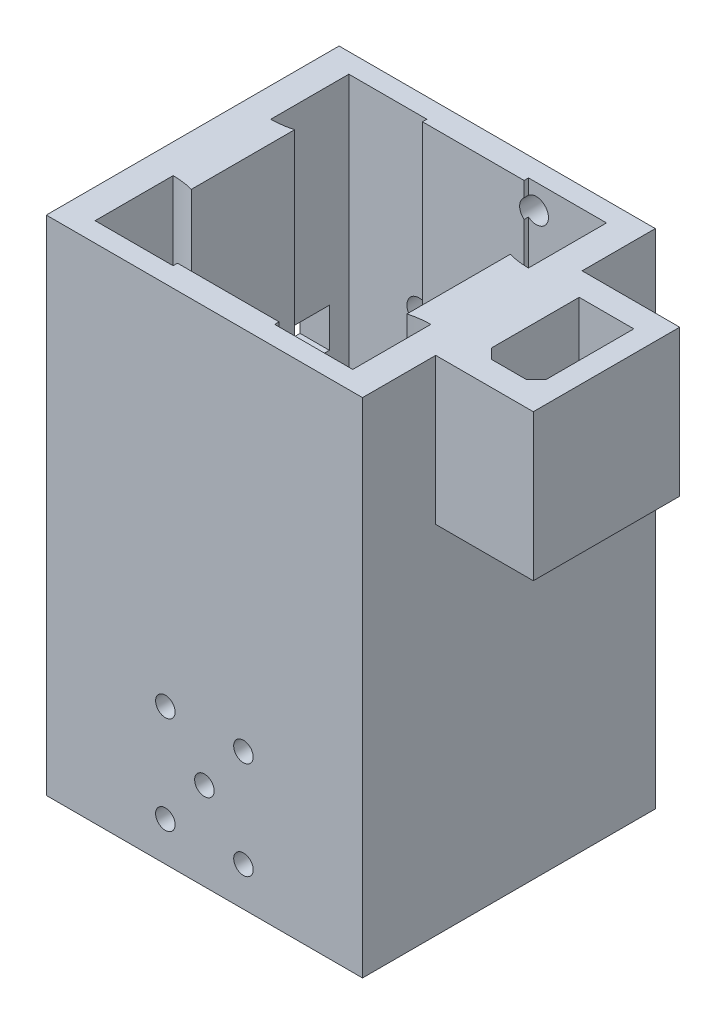
SolidWorks part; units mm, degrees
ref_plane "Front Plane" through (0, 0, 0) normal (0, 0, 1) x (1, 0, 0)
ref_plane "Top Plane" through (0, 0, 0) normal (0, 1, 0) x (1, 0, 0)
ref_plane "Right Plane" through (0, 0, 0) normal (1, 0, 0) x (0, 0, -1)
sketch "Sketch1" plane through (0, 0, 0) normal (0, 1, 0) x (1, 0, 0)
  line L0 (16.2, 0) -> (16.2, -30) construction
  line L1 (0, 0) -> (32.4, 0)
  line L2 (0, 0) -> (0, -30)
  line L3 (0, -30) -> (32.4, -30)
  line L4 (32.4, 0) -> (32.4, -30)
  line L5 (0, -15) -> (32.4, -15) construction
  circle A0 centre (6.2, -5) radius 1.75
  circle A1 centre (26.2, -5) radius 1.75
  circle A2 centre (26.2, -25) radius 1.75
  circle A3 centre (6.2, -25) radius 1.75
  dimension "D3" = 3.5
  dimension "D8" = 20
  dimension "D1" = 30
  dimension "D2" = 32.4
  dimension "D6" = 10
  dimension "D7" = 10
  dimension "D9" = 20
  dimension "D4" = 2
  dimension "D5" = 2
extrude "Boss-Extrude1" add sketch "Sketch1" along normal blind 25
sketch "Sketch2" plane through (0, 25, 0) normal (0, 1, 0) x (1, 0, 0)
  line L1 (16.2, 0) -> (16.2, -30) construction
  line L2 (32.4, 0) -> (0, 0) construction
  line L3 (0, -30) -> (32.4, -30) construction
  line L4 (0, -15) -> (32.4, -15) construction
  line L5 (0, 0) -> (0, -30) construction
  line L6 (32.4, -30) -> (32.4, 0) construction
  circle A0 centre (16.2, -15) radius 4
  dimension "D1" = 8
extrude "Cut-Extrude1" cut sketch "Sketch2" against normal blind 20
sketch "Sketch3" plane through (0, 25, 0) normal (0, 1, 0) x (1, 0, 0)
  line L0 (3, -10) -> (3, -20)
  line L1 (0, 0) -> (32.4, 0)
  line L2 (0, 0) -> (0, -30)
  line L3 (0, -30) -> (32.4, -30)
  line L4 (32.4, 0) -> (32.4, -30)
  line L5 (3, -2) -> (29.4, -2)
  line L6 (3, -2) -> (3, -28)
  line L7 (3, -28) -> (29.4, -28)
  line L8 (29.4, -2) -> (29.4, -28)
  line L9 (11, -28) -> (21.4, -28)
  line L10 (29.4, -20) -> (29.4, -10)
  line L11 (21.4, -2) -> (11, -2)
  arc A0 (11, -2) -> (3, -10) centre (3, -2) cw
  arc A1 (21.4, -28) -> (29.4, -20) centre (29.4, -28) cw
  arc A2 (29.4, -10) -> (21.4, -2) centre (29.4, -2) cw
  arc A3 (3, -20) -> (11, -28) centre (3, -28) cw
  circle M17 centre (16.2, -15) radius 4
  line M20 (0, 0) -> (0, -30)
  line M21 (0, -30) -> (32.4, -30)
  line M22 (32.4, -30) -> (32.4, 0)
  line M23 (32.4, 0) -> (0, 0)
  dimension "D5" = 8
  dimension "D6" = 8
  dimension "D7" = 8
  dimension "D8" = 8
  dimension "D1" = 3
  dimension "D2" = 3
  dimension "D3" = 2
  dimension "D4" = 2
extrude "Boss-Extrude2" add sketch "Sketch3" along normal blind 3 contours L5 L8 L7 L6 L0 M23 M20 M21 M22 | L0 A3 L7 A1 L8 A2 L5 A0 M17 region at (8.9189, 25, 7.9189) region at (16.2, 25, 0.4416)
sketch "Sketch4" plane through (0, 28, 0) normal (0, 1, 0) x (1, 0, 0)
  line L0 (16.2, 0) -> (16.2, -30) construction
  line L9 (32.4, 0) -> (0, 0) construction
  line L10 (0, -30) -> (32.4, -30) construction
  line L11 (32.4, -15) -> (0, -15) construction
  line L12 (5.15, -20.2943) -> (5.15, -9.7057)
  line L13 (0, 0) -> (0, -30) construction
  line L14 (32.4, -30) -> (32.4, 0) construction
  line L15 (29.4, -20) -> (29.4, -28) construction
  line L16 (21.4, -28) -> (29.4, -28) construction
  line L17 (3, -28) -> (11, -28) construction
  line L18 (3, -20) -> (3, -28) construction
  line L19 (3, -2) -> (11, -2) construction
  line L20 (21.4, -2) -> (29.4, -2) construction
  line L21 (29.4, -2) -> (29.4, -10) construction
  line L22 (3, -2) -> (3, -10) construction
  line L23 (0, -30) -> (32.4, -30)
  line L24 (0, 0) -> (0, -30)
  line L25 (32.4, 0) -> (0, 0)
  line L26 (32.4, -30) -> (32.4, 0)
  line L27 (29.4, -20) -> (29.4, -28)
  line L28 (21.4, -28) -> (29.4, -28)
  line L29 (3, -28) -> (11, -28)
  line L30 (3, -20) -> (3, -28)
  line L31 (3, -2) -> (11, -2)
  line L32 (21.4, -2) -> (29.4, -2)
  line L33 (29.4, -2) -> (29.4, -10)
  line L34 (3, -2) -> (3, -10)
  line L35 (10.9873, -2.45) -> (21.4127, -2.45)
  line L36 (27.25, -9.7057) -> (27.25, -20.2943)
  line L37 (10.9873, -27.55) -> (21.4127, -27.55)
  arc A0 (29.4, -20) -> (21.4, -28) centre (29.4, -28) ccw construction
  arc A1 (11, -28) -> (3, -20) centre (3, -28) ccw construction
  arc A2 (21.4, -2) -> (29.4, -10) centre (29.4, -2) ccw construction
  arc A3 (3, -10) -> (11, -2) centre (3, -2) ccw construction
  arc A4 (29.4, -20) -> (27.25, -20.2943) centre (29.4, -28) ccw
  arc A5 (11, -28) -> (10.9873, -27.55) centre (3, -28) ccw
  arc A6 (21.4, -2) -> (21.4127, -2.45) centre (29.4, -2) ccw
  arc A7 (3, -10) -> (5.15, -9.7057) centre (3, -2) ccw
  arc A8 (10.9873, -2.45) -> (11, -2) centre (3, -2) ccw
  arc A9 (5.15, -20.2943) -> (3, -20) centre (3, -28) ccw
  arc A10 (21.4127, -27.55) -> (21.4, -28) centre (29.4, -28) ccw
  arc A11 (27.25, -9.7057) -> (29.4, -10) centre (29.4, -2) ccw
  point P15 (16.2, -15)
  dimension "D1" = 22.1
  dimension "D2" = 11.05
  dimension "D3" = 25.1
  dimension "D4" = 12.55
extrude "Boss-Extrude3" add sketch "Sketch4" along normal blind 23.5
sketch "Sketch5" plane through (0, 0, 0) normal (0, 0, -1) x (-1, 0, 0)
  line L0 (-32.4, 28) -> (0, 28) construction
  line L1 (-32.4, 28) -> (0, 28)
  line L2 (-5.15, 28) -> (-5.15, 36.9803) construction
  line L3 (0, 51.5) -> (0, 0) construction
  line L4 (-27.25, 28) -> (-27.25, 39.4314) construction
  line L5 (-32.4, 51.5) -> (-32.4, 0) construction
  line L6 (-16.2, 28) -> (-16.2, 36.5707) construction
  circle A0 centre (-22.2, 49) radius 1.25
  circle A1 centre (-10.2, 34) radius 1.25
  dimension "D6" = 2.5
  dimension "D7" = 2.5
  dimension "D1" = 6
  dimension "D2" = 12
  dimension "D3" = 5.15
  dimension "D4" = 5.15
  dimension "D5" = 6
  dimension "D8" = 15
extrude "Cut-Extrude2" cut sketch "Sketch5" along direction (0, 0, 1) on the side against the normal up to surface (2.45 mm away) contours A0 | A1 region at (22.2, 49, 0) region at (10.2, 34, 0) up to face at (16.2, 39.75, 2.45)
sketch "Sketch6" plane through (0, 0, 0) normal (-1, 0, 0) x (0, 0, 1)
  line L0 (0, 28) -> (30, 28) construction
  line L1 (0, 28) -> (30, 28)
  line L2 (0, 51.5) -> (0, 0) construction
  line L3 (4, 28) -> (26, 28)
  line L4 (4, 28) -> (4, 32)
  line L5 (4, 32) -> (26, 32)
  line L6 (26, 28) -> (26, 32)
  line L7 (30, 51.5) -> (30, 0) construction
  dimension "D1" = 4
  dimension "D2" = 4
  dimension "D3" = 4
extrude "Cut-Extrude3" cut sketch "Sketch6" along direction (1, 0, 0) on the side against the normal up to surface (5.15 mm away) contours L1 L6 L5 L4 region at (0, 30, 15) up to face at (5.15, 39.75, 15)
sketch "Sketch7" plane through (32.4, 0, 0) normal (1, 0, 0) x (0, 0, -1)
  line L1 (-7.5, 51.5) -> (-22.5, 51.5)
  line L2 (-7.5, 51.5) -> (-7.5, 36.5)
  line L3 (-7.5, 36.5) -> (-22.5, 36.5)
  line L4 (-22.5, 51.5) -> (-22.5, 36.5)
  line L5 (-30, 51.5) -> (0, 51.5) construction
  point P6 (-15, 51.5)
  dimension "D1" = 15
  dimension "D3" = 15
extrude "Boss-Extrude4" add sketch "Sketch7" along normal blind 10
sketch "Sketch8" plane through (0, 51.5, 0) normal (0, 1, 0) x (1, 0, 0)
  line L0 (32.4, 0) -> (32.4, -30) construction
  line L1 (34.6, -10) -> (40.2, -10)
  line L2 (34.6, -10) -> (34.6, -20)
  line L3 (34.6, -20) -> (40.2, -20)
  line L4 (40.2, -10) -> (40.2, -20)
  line L5 (42.4, -7.5) -> (32.4, -7.5) construction
  point P6 (32.4, -15)
  point P7 (34.6, -15)
  point P8 (37.4, -7.5)
  point P11 (37.4, -10)
  dimension "D1" = 5.6
  dimension "D2" = 10
extrude "Cut-Extrude4" cut sketch "Sketch8" against normal through all
chamfer "Chamfer1" distance 1 angle 45 2 edges at (40.2, 44, 20) (34.6, 44, 20)
sketch "Sketch11" plane through (0, 0, 30) normal (0, 0, 1) x (1, 0, 0)
  line L0 (0, 0) -> (32.4, 0) construction
  line L2 (12.2, 14) -> (20.2, 14) construction
  line L3 (12.2, 14) -> (12.2, 4) construction
  circle A0 centre (12.2, 14) radius 1
  circle A1 centre (20.2, 14) radius 1
  circle A2 centre (12.2, 4) radius 1
  circle A3 centre (20.2, 4) radius 1
  circle A4 centre (16.2, 9) radius 1
  point P6 (16.2, 14)
  point P13 (12.2, 9)
  dimension "D1" = 2
  dimension "D2" = 2
  dimension "D3" = 2
  dimension "D4" = 2
  dimension "D5" = 4
  dimension "D6" = 8
  dimension "D8" = 2
  dimension "D7" = 10
extrude "Cut-Extrude5" cut sketch "Sketch11" against normal blind 10
